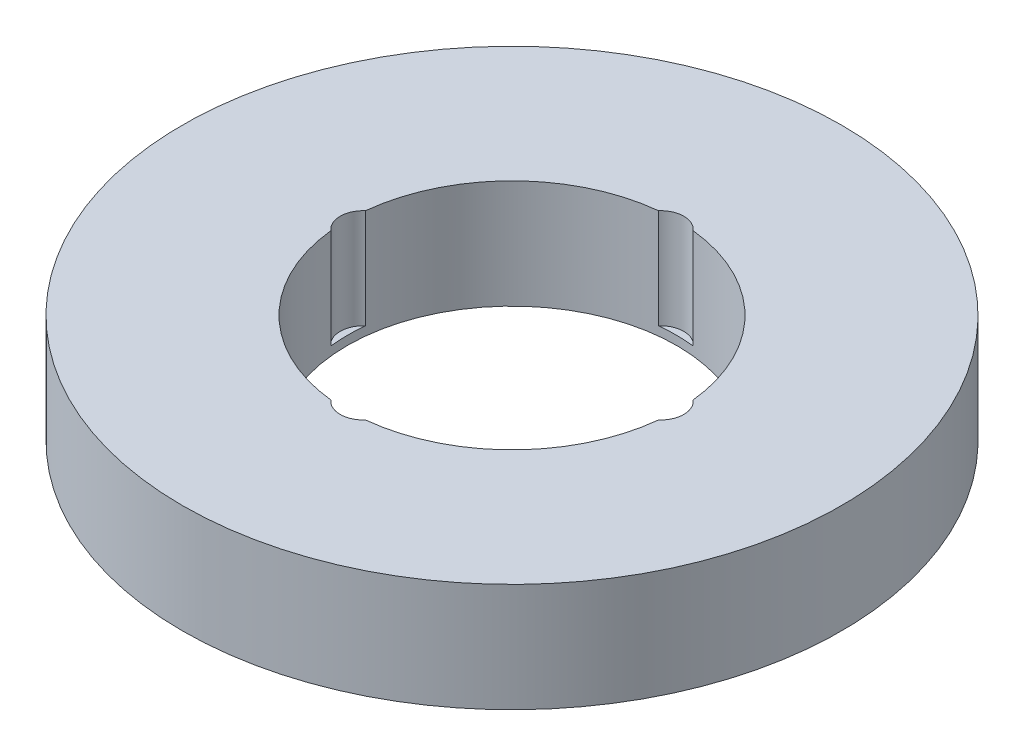
SolidWorks part; units mm, degrees
ref_plane "Front Plane" through (0, 0, 0) normal (0, 0, 1) x (1, 0, 0)
ref_plane "Top Plane" through (0, 0, 0) normal (0, 1, 0) x (1, 0, 0)
ref_plane "Right Plane" through (0, 0, 0) normal (1, 0, 0) x (0, 0, -1)
sketch "Sketch1" plane through (0, 0, 0) normal (0, 1, 0) x (1, 0, 0)
  circle A0 centre (0, 0) radius 85
  dimension "FLANGE_OD" = 170
extrude "Boss-Extrude1" add sketch "Sketch1" along normal blind 28
sketch "Sketch2" plane through (0, 0, 0) normal (0, 1, 0) x (1, 0, 0)
  circle A0 centre (0, 0) radius 42.5
  dimension "BORE_D" = 85
extrude "Cut-Extrude1" cut sketch "Sketch2" along normal through all
sketch "Sketch3" plane through (0, 28, 0) normal (0, 1, 0) x (1, 0, 0)
  circle A0 centre (0, 0) radius 38.362 construction
  circle A1 centre (-38.362, 0) radius 5.9371
  dimension "BOLT_D" = 11.8743
  dimension "BOLT_PCD" = 76.7239
extrude "Cut-Extrude2" cut sketch "Sketch3" against normal blind 25.7225
pattern_circular "CirPattern1" count 4 over 360 about axis through (0, 0, 0) along (0, 1, 0) of "Cut-Extrude2"
